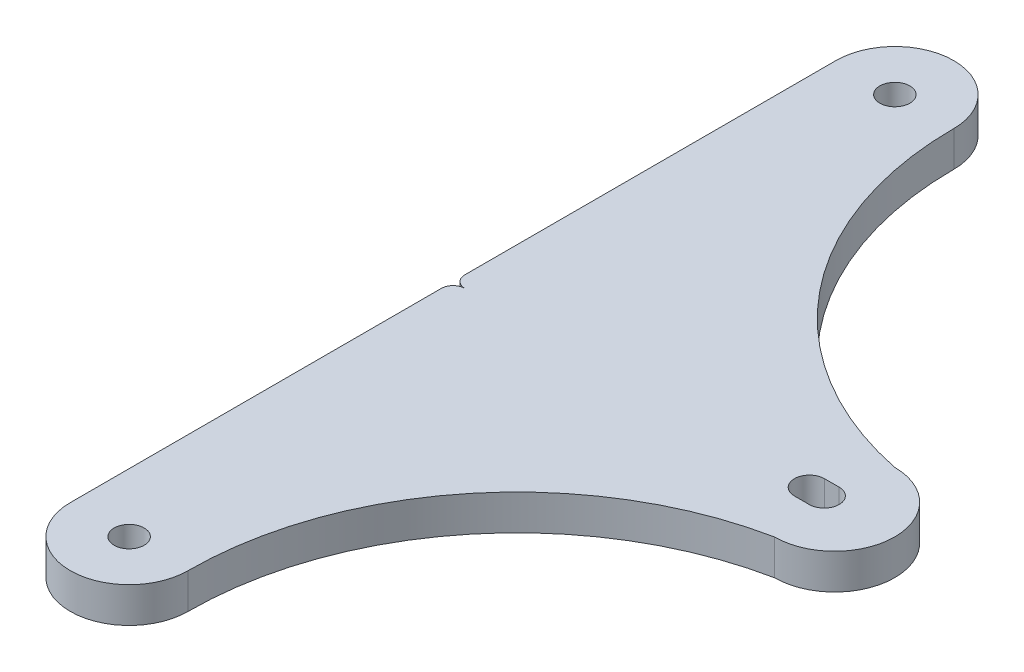
SolidWorks part; units mm, degrees
material "Клен"
ref_plane "Спереди" through (0, 0, 0) normal (0, 0, 1) x (1, 0, 0)
ref_plane "Сверху" through (0, 0, 0) normal (0, 1, 0) x (1, 0, 0)
ref_plane "Справа" through (0, 0, 0) normal (1, 0, 0) x (0, 0, -1)
sketch "Эскиз1" plane through (0, 0, 0) normal (0, 1, 0) x (1, 0, 0)
  line L0 (-41.181, -0.0464) -> (44.1026, -0.0464) construction
  line L11 (-35, -65) -> (-35, 65)
  arc A8 (-35, 65) -> (-15, 65) centre (-25, 65) cw
  arc A9 (-35, -65) -> (-15, -65) centre (-25, -65) ccw
  arc A10 (29.8091, 10.176) -> (29.8091, -10.2688) centre (29.8091, -0.0464) cw
  arc A13 (-15, -65) -> (29.8091, -10.2688) centre (40.8297, -65) cw
  arc A14 (-15, 65) -> (29.8091, 10.176) centre (40.9431, 65) ccw
  point P0 (0, 0)
extrude "Бобышка-Вытянуть1" add sketch "Эскиз1" along normal blind 6
sketch "Эскиз2" plane through (0, 0, 0) normal (0, -1, 0) x (1, 0, 0)
  line L4 (28, 0) -> (25.5, 0) construction
  line L5 (28, -2.55) -> (25.5, -2.55)
  line L6 (-46.1924, 0) -> (55.6646, 0) construction
  line L7 (28, 2.55) -> (25.5, 2.55)
  circle A0 centre (-25, -65) radius 2.55
  circle A5 centre (-25, 65) radius 2.55
  arc A6 (28, -2.55) -> (28, 2.55) centre (28, 0) ccw
  arc A7 (25.5, 2.55) -> (25.5, -2.55) centre (25.5, 0) ccw
  arc A8 (-35, -65) -> (-15, -65) centre (-25, -65) ccw construction
  point P6 (151.7105, -58.5237)
  point P13 (26.75, 0)
  dimension "D1" = 5.1
  dimension "D7" = 5.1
  dimension "D8" = 2.5
  dimension "D9" = 53
extrude "Вырез-Вытянуть1" cut sketch "Эскиз2" against normal through all
sketch "Эскиз3" plane through (0, 0, 0) normal (0, -1, 0) x (1, 0, 0)
  line L0 (-33, 0) -> (27.7687, 0) construction
  line L1 (-35, -65) -> (-35, 65) construction
  line L2 (-35, -2) -> (-35, 2)
  arc A0 (-33, 0) -> (-35, -2) centre (-33, -2) ccw
  arc A1 (-33, 0) -> (-35, 2) centre (-33, 2) cw
  point P3 (-35, -2)
  point P4 (-33, 0)
  point P7 (-35, 2)
  dimension "D2" = 2
  dimension "D1" = 2
extrude "Вырез-Вытянуть2" cut sketch "Эскиз3" against normal through all
